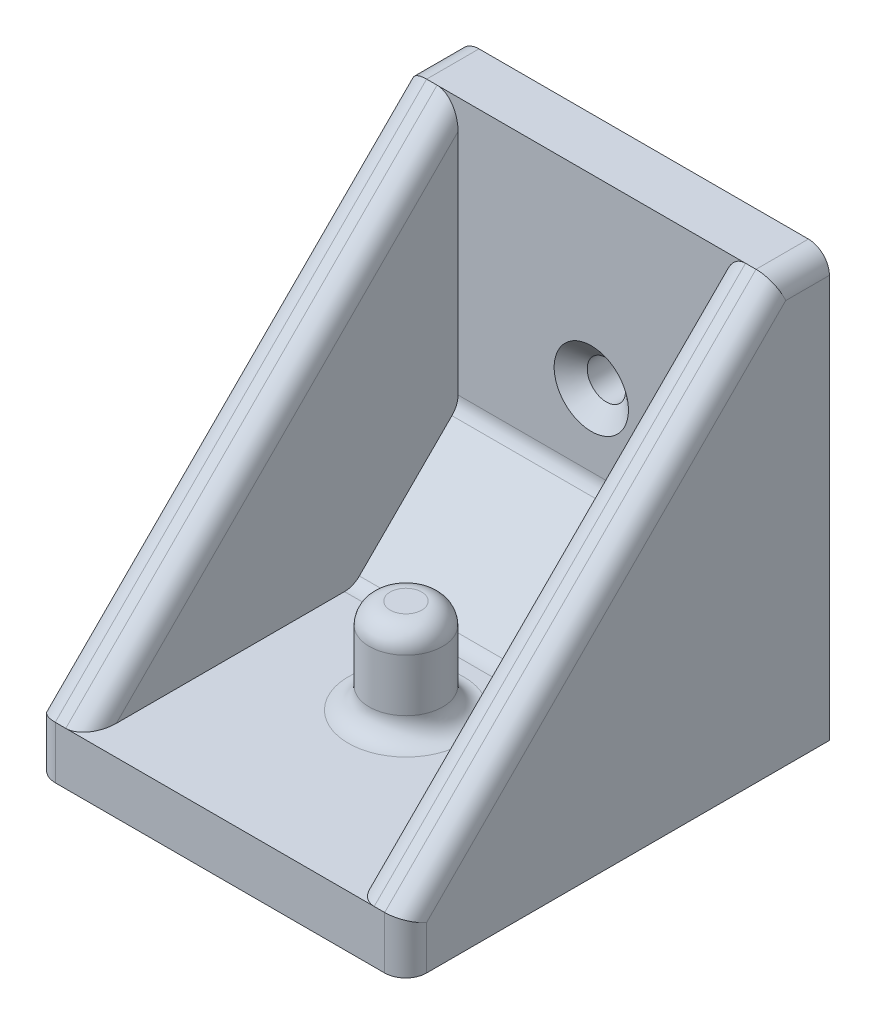
SolidWorks part; units mm, degrees
ref_plane "Front Plane" through (0, 0, 0) normal (0, 0, 1) x (1, 0, 0)
ref_plane "Top Plane" through (0, 0, 0) normal (0, 1, 0) x (1, 0, 0)
ref_plane "Right Plane" through (0, 0, 0) normal (1, 0, 0) x (0, 0, -1)
sketch "Sketch1" plane through (0, 0, 0) normal (0, 0, 1) x (1, 0, 0)
  line L1 (0, 0) -> (35.42, 0)
  line L2 (0, 0) -> (0, 35.42)
  line L3 (0, 35.42) -> (35.42, 35.42)
  line L4 (35.42, 0) -> (35.42, 35.42)
  dimension "D1" = 35.42
  dimension "D2" = 35.42
extrude "Boss-Extrude1" add sketch "Sketch1" along normal blind 5
sketch "Sketch6" plane through (0, 0, 0) normal (0, -1, 0) x (1, 0, 0)
  line L0 (0, -2.75) -> (0, 2.75) construction
  line L1 (35.42, 5) -> (0, 5)
  line L2 (35.42, 5) -> (35.42, 40.42)
  line L3 (35.42, 40.42) -> (0, 40.42)
  line L4 (0, 5) -> (0, 40.42)
  line L5 (19.481, 0) -> (-19.481, 0) construction
  line L6 (0, 5) -> (35.42, 5)
  line L7 (0, 5) -> (0, 0)
  line L8 (0, 0) -> (35.42, 0)
  line L9 (35.42, 5) -> (35.42, 0)
  line M2 (0, 0) -> (35.42, 0)
  line M3 (35.42, 0) -> (35.42, 5)
  line M4 (35.42, 5) -> (0, 5)
  line M5 (0, 5) -> (0, 0)
  dimension "D1" = 35.42
extrude "Boss-Extrude2" add sketch "Sketch6" along normal blind 5 contours M5 M2 M3 M4 | L4 L2 L3 M4 region at (17.71, 0, 2.5) region at (17.71, 0, 22.71)
sketch "Sketch7" plane through (0, 0, 0) normal (-1, 0, 0) x (0, 0, 1)
  line L0 (5, 35.42) -> (40.42, 0)
  line L1 (19.481, 0) -> (-19.481, 0) construction
  line L2 (40.42, 0) -> (5, 0)
  line L3 (5, 35.42) -> (5, 0) construction
  line L4 (5, 0) -> (5, 35.42)
extrude "Boss-Extrude3" add sketch "Sketch7" against normal blind 5
sketch "Sketch8" plane through (35.42, 0, 0) normal (1, 0, 0) x (0, 0, -1)
  line L0 (-40.42, 0) -> (-5, 35.42)
  line L1 (19.481, 0) -> (-19.481, 0) construction
  line L2 (-40.42, -5) -> (-40.42, 0) construction
  line L3 (-5, 35.42) -> (-5, 0)
  line L4 (-5, 0) -> (-5, 35.42) construction
  line L5 (-5, 0) -> (-40.42, 0)
extrude "Boss-Extrude4" add sketch "Sketch8" against normal blind 5
hole_wizard "CSK for #6 Flat Head Machine Screw (100)2" positions "Sketch9" profile "Sketch10" countersink size "#6" standard "ANSI Inch" end condition through all
sketch "Sketch9" plane through (0, 0, 5) normal (0, 0, 1) x (1, 0, 0)
  line L0 (35.42, 0) -> (0, 35.42)
  line L1 (19.481, 0) -> (-19.481, 0) construction
  line L2 (35.42, -5) -> (35.42, 0) construction
  line L3 (0, -22.231) -> (0, 22.231) construction
  line L4 (5, 35.42) -> (0, 35.42) construction
  point P13 (17.71, 17.71)
sketch "Sketch10" plane through (17.71, 17.71, 5) normal (1, 0, 0) x (0, -1, 0)
  line L0 (0, 0) -> (0, 5)
  line L1 (0, 5) -> (1.8288, 5)
  line L2 (1.8288, 5) -> (1.8288, 1.4386)
  line L3 (1.8288, 1.4386) -> (3.5433, 0)
  line L5 (3.5433, 0) -> (0, 0)
  line L6 (-1.8288, 1.4386) -> (-3.5433, 0) construction
  line L11 (0, -6.35) -> (0, 107.95) construction
  dimension "Thru Hole Dia." = 3.6576
  dimension "Thru Hole Depth" = 5
  dimension "Near C'Sink Dia." = 7.0866
  dimension "Near C'Sink Angle" = 100
sketch "Sketch11" plane through (0, 0, 0) normal (0, 1, 0) x (1, 0, 0)
  line L0 (0, -40.3586) -> (35.42, -5)
  line L1 (0, -22.231) -> (0, 22.231) construction
  circle A0 centre (17.71, -22.6793) radius 3.5
extrude "Boss-Extrude5" add sketch "Sketch11" along normal blind 9 contours L0 A0 | L0 A0 region at (16.6605, 0, 21.628) region at (18.7595, 0, 23.7306)
sketch "Sketch12" plane through (0, 9, 0) normal (0, 1, 0) x (1, 0, 0)
  circle A0 centre (17.71, -22.6793) radius 1.1
extrude "Cut-Extrude1" cut sketch "Sketch12" against normal up to surface (14 mm away) from offset 5 up to face at (17.71, -5, 20.21) offset against normal yes
chamfer "Chamfer1" distance 10 angle 45 1 edges at (17.71, 0, 5)
fillet "Fillet2" radius 2 13 edges at (17.71, 9, 26.1793) (17.71, 10, 5) (17.71, 0, 15) (17.71, 0, 19.1793) (17.71, -5, 21.5793) (5, 17.71, 22.71) (30.42, 17.71, 22.71) (35.42, 17.71, 22.71) (0, 17.71, 22.71) (0, -2.5, 40.42) (35.42, -2.5, 40.42) (35.42, 35.42, 2.5) (0, 35.42, 2.5)
